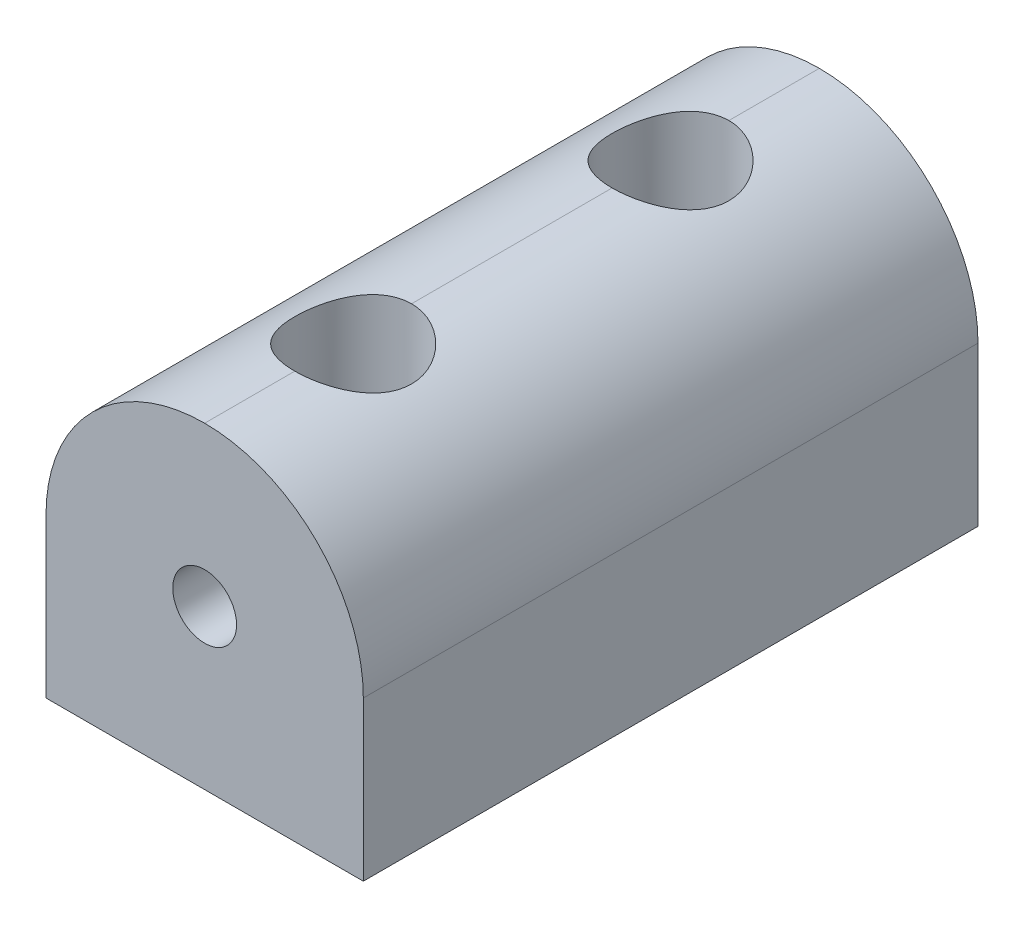
SolidWorks part; units mm, degrees
ref_plane "Front"
ref_plane "Top" through (0, 0, 0) normal (0, 1, 0) x (1, 0, 0)
ref_plane "Right" through (0, 0, 0) normal (1, 0, 0) x (0, 0, -1)
sketch "Sketch1" plane through (0, 0, 0) normal (0, 0, 1) x (1, 0, 0)
  line L1 (-12.7, 0) -> (12.7, 0)
  line L2 (12.7, 0) -> (12.7, 12.7)
  line L3 (-12.7, 0) -> (-12.7, 25.4)
  line L4 (0, 25.4) -> (-12.7, 25.4)
  arc A0 (12.7, 12.7) -> (0, 25.4) centre (0, 12.7) ccw
  point P6 (0, 0)
  point P7 (0, 0)
  dimension "D3" = 12.7
  dimension "D1" = 25.4
  dimension "D2" = 25.4
extrude "Extrude1" add sketch "Sketch1" against normal blind 49.1998
hole_wizard "1/4-20 Tapped Hole2" positions "Sketch6" profile "Sketch5" tap size "1/4-20" standard "Ansi Inch"
sketch "Sketch6" plane through (0, 0, 0) normal (0, 0, 1) x (1, 0, 0)
  line L0 (-12.7, 25.4) -> (-12.7, 0) construction
  line L1 (-12.7, 0) -> (12.7, 0) construction
  point P0 (0, 12.7)
  dimension "D1" = 12.7
  dimension "D2" = 12.7
cosmetic thread "Cosmetic Thread2" parameters "D1"=12.7, "D2"=6.35
sketch "Sketch5" plane through (0, 12.7, 0) normal (1, 0, 0) x (0, -1, 0)
  line L0 (0, 0) -> (0, 26.9338)
  line L1 (0, 26.9338) -> (2.5527, 25.4)
  line L2 (2.5527, 25.4) -> (2.5527, 0)
  line L5 (2.5527, 0) -> (0, 0)
  line L10 (0, 26.9338) -> (-2.5527, 25.4) construction
  line L11 (0, -6.35) -> (0, 107.95) construction
  dimension "Tap Drill Dia." = 5.1054
  dimension "Tap Drill Depth" = 25.4
  dimension "Drill Angle" = 118
hole_wizard "1/4-20 Tapped Hole4" positions "Sketch14" profile "Sketch13" tap size "1/4-20" standard "Ansi Inch"
sketch "Sketch14" plane through (0, 0, -49.1998) normal (0, 0, -1) x (-1, 0, 0)
  circle A0 centre (0, 12.7) radius 2.5527 construction
  point P0 (0, 12.7)
cosmetic thread "Cosmetic Thread4" parameters "D1"=12.7, "D2"=6.35
sketch "Sketch13" plane through (0, 12.7, -49.1998) normal (1, 0, 0) x (0, 1, 0)
  line L0 (0, 0) -> (0, 26.9338)
  line L1 (0, 26.9338) -> (2.5527, 25.4)
  line L2 (2.5527, 25.4) -> (2.5527, 0)
  line L5 (2.5527, 0) -> (0, 0)
  line L10 (0, 26.9338) -> (-2.5527, 25.4) construction
  line L11 (0, -6.35) -> (0, 107.95) construction
  dimension "Tap Drill Dia." = 5.1054
  dimension "Tap Drill Depth" = 25.4
  dimension "Drill Angle" = 118
hole_wizard "CBORE for 1/4 Socket Head Cap Screw1" positions "Sketch11" profile "Sketch10" counterbore size "1/4" standard "Ansi Inch"
sketch "Sketch11" plane through (0, 25.4, 0) normal (0, 1, 0) x (-1, 0, 0)
  line L0 (12.7, -49.1998) -> (12.7, 0) construction
  line L1 (0, 0) -> (12.7, 0) construction
  point P0 (0, -11.8872)
  point P5 (0, -37.2872)
  dimension "D1" = 12.7
  dimension "D2" = 11.8872
  dimension "D3" = 25.4
sketch "Sketch10" plane through (0, 25.4, -11.8872) normal (1, 0, 0) x (0, 0, 1)
  line L0 (0, 0) -> (0, 25.4)
  line L1 (0, 25.4) -> (3.2639, 25.4)
  line L3 (3.2639, 25.4) -> (3.2639, 7.9248)
  line L4 (3.2639, 7.9248) -> (4.6736, 7.9248)
  line L5 (4.6736, 7.9248) -> (4.6736, 0)
  line L7 (4.6736, 0) -> (0, 0)
  line L11 (0, -6.35) -> (0, 107.95) construction
  dimension "Thru Hole Dia." = 6.5278
  dimension "Thru Hole Depth" = 25.4
  dimension "C'Bore Dia." = 9.3472
  dimension "C'Bore Depth" = 7.9248
fillet "Fillet1" radius 12.7
